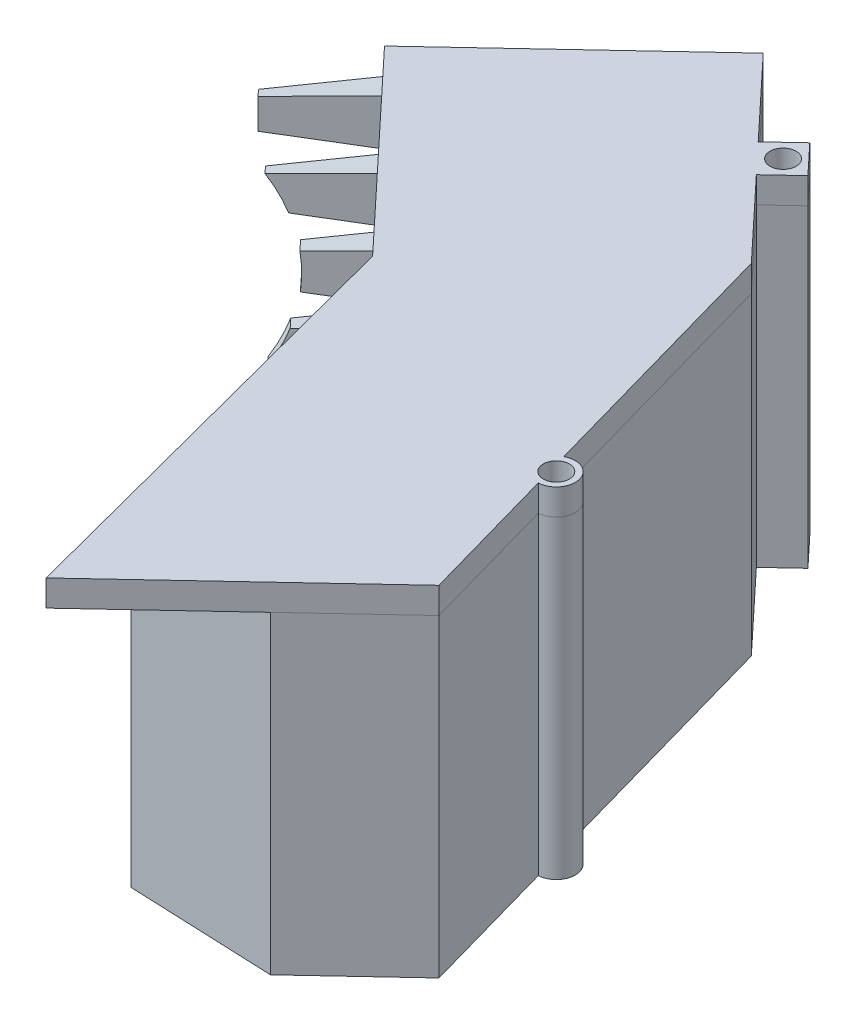
SolidWorks part; units mm, degrees
ref_plane "Front Plane" through (0, 0, 0) normal (0, 0, 1) x (1, 0, 0)
ref_plane "Top Plane" through (0, 0, 0) normal (0, 1, 0) x (1, 0, 0)
ref_plane "Right Plane" through (0, 0, 0) normal (1, 0, 0) x (0, 0, -1)
sketch "Sketch1" plane through (0, 0, 0) normal (0, 1, 0) x (1, 0, 0)
  line L0 (-4.2088, -43.4753) -> (11.4751, 13.8639) construction
  line L1 (15.2438, 108.2324) -> (-2.7837, 127.4797) construction
  line L2 (-27.496, 153.8638) -> (-74.9669, 109.4011) construction
  line L3 (11.4751, 13.8639) -> (-32.8086, 77.4293) construction
  line L4 (15.2438, 108.2324) -> (33.1183, 44.8363) construction
  line L5 (45.0177, 2.6318) -> (-4.2088, -43.4753) construction
  line L6 (-4.2088, -43.4753) -> (-32.2271, 63.7697) construction
  line L7 (45.0177, 2.6318) -> (35.5507, 36.2092)
  line L8 (15.2438, 108.2324) -> (-2.7837, 127.4797)
  line L9 (-27.496, 153.8638) -> (-74.9669, 109.4011)
  line L10 (-74.9669, 109.4011) -> (-32.2271, 63.7697)
  line L11 (-32.2271, 63.7697) -> (-4.2088, -43.4753)
  line L13 (45.0177, 2.6318) -> (-4.2088, -43.4753)
  line L15 (35.5507, 36.2092) -> (45.0177, 2.6318) construction
  line L16 (33.1183, 44.8363) -> (15.2438, 108.2324)
  line L17 (-32.8086, 77.4293) -> (-1.2, 109.0418) construction
  line L18 (20.4045, -20.4217) -> (11.4751, 13.8639) construction
  line L19 (-4.2088, -43.4753) -> (-17.3046, 6.6513) construction
  line L20 (0.3363, 130.3833) -> (0.3273, 130.3935) construction
  line L21 (-17.3046, 6.6513) -> (11.4751, 13.8639) construction
  line L22 (-6.1168, 137.7559) -> (-9.4684, 134.6166) construction
  line L23 (-3.0026, 140.4816) -> (-2.8851, 140.5844) construction
  line L24 (-17.3046, 6.6513) -> (-13.163, 7.6893) construction
  line L25 (-13.163, 7.6893) -> (-27.9465, 65.5328) construction
  line L26 (3.679, 133.5328) -> (-2.7837, 127.4797)
  line L27 (3.679, 133.5328) -> (-3.0057, 140.6698)
  line L29 (-3.0057, 140.6698) -> (-9.4684, 134.6166)
  line L30 (-51.2315, 131.6325) -> (-48.4968, 128.2564) construction
  line L31 (-48.4968, 128.2564) -> (-27.496, 147.9264) construction
  line L32 (-9.4684, 134.6166) -> (-27.496, 153.8638) construction
  line L33 (-9.4684, 134.6166) -> (-27.496, 153.8638)
  line L34 (-3.0026, 140.4816) -> (-3.0057, 140.6698) construction
  line L35 (-27.496, 147.9264) -> (-23.2222, 143.3634) construction
  line L36 (0.3273, 130.3935) -> (0.3363, 130.3833) construction
  line L37 (-23.2222, 143.3634) -> (-20.2598, 146.1381) construction
  line L38 (-23.2222, 143.3634) -> (9.6827, 108.2324) construction
  line L39 (24.1811, 76.5343) -> (20.2695, 75.4315) construction
  line L40 (20.2695, 75.4315) -> (13.2737, 100.2435) construction
  line L41 (20.2695, 75.4315) -> (27.658, 49.2262) construction
  line L42 (27.658, 49.2262) -> (31.4686, 35.7107) construction
  line L43 (31.4686, 35.7107) -> (34.5448, 24.4916) construction
  line L44 (12.1112, 105.39) -> (13.2737, 100.2435) construction
  line L45 (9.6827, 108.2324) -> (12.1112, 105.39) construction
  line L46 (-53.597, 86.5854) -> (-50.4371, 89.545) construction
  line L47 (-50.4371, 89.545) -> (-71.8071, 112.3607) construction
  line L48 (-48.4968, 128.2564) -> (-68.8447, 109.1979) construction
  line L49 (-68.8447, 109.1979) -> (-50.4371, 89.545) construction
  line L50 (-50.4371, 89.545) -> (-27.9465, 65.5328) construction
  line L51 (-68.8447, 109.1979) -> (-27.9465, 65.5328)
  line L52 (-27.9465, 65.5328) -> (-13.163, 7.6893)
  line L53 (-68.8447, 109.1979) -> (-27.496, 147.9264)
  line L54 (-27.496, 147.9264) -> (12.1112, 105.39)
  line L55 (12.1112, 105.39) -> (34.5448, 24.4916)
  arc A1 (35.5507, 36.2092) -> (33.1183, 44.8363) centre (35.3343, 40.8046) ccw
  circle A4 centre (-2.8946, 134.0748) radius 3.175
  circle A5 centre (35.3343, 40.8046) radius 3.175
  circle A6 centre (11.4751, 13.8639) radius 25.4
  circle A7 centre (-32.8086, 77.4293) radius 3.175
  circle A8 centre (-1.2, 109.0418) radius 3.175
  dimension "D1" = 6.35
  dimension "D2" = 6.35
  dimension "D3" = 59.4455
  dimension "D5" = 50.8
  dimension "D8" = 6.35
  dimension "D4" = 31.576
  dimension "D6" = 77.47
  dimension "D7" = 129.839
  dimension "D9" = 44.704
  dimension "D10" = 100.14
  dimension "D11" = 35.4294
  dimension "D12" = 4.2697
ref_plane "Plane1" through (0, 0, 0) normal (0, 1, 0) x (1, 0, 0)
sketch "Sketch4" plane through (0, 0, 0) normal (0, 1, 0) x (1, 0, 0)
  line L0 (-68.8447, 109.1979) -> (-27.9465, 65.5328)
  line L1 (-27.9465, 65.5328) -> (-13.1495, 7.6432)
  line L2 (-68.8447, 109.1979) -> (-27.496, 147.9264)
  line L3 (-27.496, 147.9264) -> (12.1112, 105.39)
  line L4 (12.1112, 105.39) -> (34.5583, 24.4455)
  circle A0 centre (-2.8946, 134.0748) radius 3.175
  circle A1 centre (35.3343, 40.8046) radius 3.175
  circle A2 centre (11.4751, 13.8639) radius 25.393
  circle A3 centre (-32.8086, 77.4293) radius 3.175
  circle A4 centre (-1.2, 109.0418) radius 3.175
extrude "Boss-Extrude2" add sketch "Sketch1" along normal blind 76.2 contours L7 A1 L16 L8 L26 L27 L29 L33 L9 L10 L11 L13 A6 L52 L51 L53 L54 L55 A5 A4 region at (18.8257, 0, 18.7361)
extrude "Boss-Extrude3" add sketch "Sketch1<5>" along normal blind 6.35 contours A6 L55 L54 L53 L51 L52 A8 A7 region at (-15.1101, 0, -86.0279)
sketch "Sketch1<5>" plane through (0, 0, 0) normal (0, 1, 0) x (1, 0, 0) same geometry as "Sketch1"
ref_plane "Plane2" through (0, 76.2, 0) normal (0, 1, 0) x (1, 0, 0)
sketch "Sketch5" plane through (0, 76.2, 0) normal (0, 1, 0) x (1, 0, 0)
  line L0 (45.0177, 2.6318) -> (35.5507, 36.2092)
  line L1 (15.2438, 108.2324) -> (-2.7837, 127.4797)
  line L2 (-27.496, 153.8638) -> (-74.9669, 109.4011)
  line L3 (-74.9669, 109.4011) -> (-32.2271, 63.7697)
  line L4 (-32.2271, 63.7697) -> (-4.2088, -43.4753)
  line L5 (45.0177, 2.6318) -> (-4.2088, -43.4753)
  line L6 (33.1183, 44.8363) -> (15.2438, 108.2324)
  line L7 (3.679, 133.5328) -> (-2.7837, 127.4797)
  line L8 (3.679, 133.5328) -> (-3.0057, 140.6698)
  line L9 (-3.0057, 140.6698) -> (-9.4684, 134.6166)
  line L10 (-9.4684, 134.6166) -> (-27.496, 153.8638)
  line L11 (45.0177, 2.6318) -> (35.5507, 36.2092) construction
  line L12 (-74.9669, 109.4011) -> (-32.2271, 63.7697) construction
  circle A1 centre (-2.8946, 134.0748) radius 3.175
  arc A3 (35.5507, 36.2092) -> (33.1183, 44.8363) centre (35.3343, 40.8046) ccw construction
  arc A4 (35.5507, 36.2092) -> (33.1183, 44.8363) centre (35.3343, 40.8046) ccw
  circle A5 centre (35.3343, 40.8046) radius 3.175
extrude "Boss-Extrude4" add sketch "Sketch5" along normal blind 6.35 separate body
ref_plane "Plane3" through (14.6497, 0, -13.7214) normal (-0.7299, 0, 0.6836) x (0.6836, 0, 0.7299)
sketch "Sketch6" plane through (14.6497, 0, -13.7214) normal (-0.7299, 0, 0.6836) x (0.6836, 0, 0.7299)
  line L0 (-99.8337, 82.55) -> (-99.8337, 0) construction
  line L4 (-99.8337, 66.675) -> (-99.8337, 15.875) construction
  line L6 (-125.2337, 66.675) -> (-74.4337, 66.675)
  line L7 (-125.2337, 66.675) -> (-125.2337, 15.875)
  line L8 (-125.2337, 15.875) -> (-74.4337, 15.875)
  line L9 (-74.4337, 66.675) -> (-74.4337, 15.875)
  line L11 (-131.0944, 82.55) -> (-68.573, 82.55) construction
  line L12 (65.9916, 0) -> (-65.9916, 0) construction
  line L13 (-131.0944, 38.1) -> (-68.573, 38.1) construction
  line L14 (-131.0944, 76.2) -> (-131.0944, 0) construction
  line L15 (-68.573, 76.2) -> (-68.573, 0) construction
  line L16 (-125.2337, 41.275) -> (-74.4337, 41.275) construction
  point P4 (-99.8337, 82.55)
  point P6 (-131.0944, 41.275)
  point P20 (-99.8337, 41.275)
  point P23 (-99.8337, 41.275)
  dimension "D1" = 50.8
  dimension "D2" = 50.8
extrude "Cut-Extrude1" cut sketch "Sketch6" against normal blind 21.59
sketch "Sketch7" plane through (14.6497, 0, -13.7214) normal (-0.7299, 0, 0.6836) x (0.6836, 0, 0.7299)
  line L0 (-125.2337, 66.675) -> (-125.2337, 15.875) construction
  line L1 (-131.0944, 76.1681) -> (-125.2337, 76.1681)
  line L2 (-131.0944, 76.1681) -> (-131.0944, 65.0458)
  line L3 (-131.0944, 65.0458) -> (-125.2337, 65.0458)
  line L4 (-125.2337, 76.1681) -> (-125.2337, 65.0458)
  line L5 (-131.0944, 48.7843) -> (-125.2337, 48.7843)
  line L6 (-125.2337, 59.9067) -> (-125.2337, 48.7843)
  line L7 (-131.0944, 59.9067) -> (-125.2337, 59.9067)
  line L8 (-131.0944, 59.9067) -> (-131.0944, 48.7843)
  line L9 (-131.0944, 32.5229) -> (-125.2337, 32.5229)
  line L10 (-125.2337, 43.6452) -> (-125.2337, 32.5229)
  line L11 (-131.0944, 43.6452) -> (-125.2337, 43.6452)
  line L12 (-131.0944, 43.6452) -> (-131.0944, 32.5229)
  line L13 (-131.0944, 16.2614) -> (-125.2337, 16.2614)
  line L14 (-125.2337, 27.3838) -> (-125.2337, 16.2614)
  line L15 (-131.0944, 27.3838) -> (-125.2337, 27.3838)
  line L16 (-131.0944, 27.3838) -> (-131.0944, 16.2614)
  line L17 (-131.0944, 0) -> (-125.2337, 0)
  line L18 (-125.2337, 11.1223) -> (-125.2337, 0)
  line L19 (-131.0944, 11.1223) -> (-125.2337, 11.1223)
  line L20 (-131.0944, 11.1223) -> (-131.0944, 0)
  line L21 (-131.0944, 0) -> (-68.573, 0) construction
  line L22 (-131.0944, 76.2) -> (-131.0944, 0) construction
  dimension "D2" = 5
extrude "Boss-Extrude5" add sketch "Sketch7" along normal blind 21.59 draft 5
ref_plane "Plane4" through (-89.6167, 0, -95.6796) normal (-0.6836, 0, -0.7299) x (-0.7299, 0, 0.6836)
sketch "Sketch10" plane through (-89.6167, 0, -95.6796) normal (-0.6836, 0, -0.7299) x (-0.7299, 0, 0.6836)
  circle A0 centre (30.057, 37.7452) radius 36.0519
extrude "Cut-Extrude2" cut sketch "Sketch10" against normal blind 21.59
ref_plane "Plane5" through (-0.4558, 0, 11.0662) normal (0.0412, 0, -0.9992) x (0, -1, 0)
sketch "Sketch11" plane through (-0.4558, 0, 11.0662) normal (0.0412, 0, -0.9992) x (0, -1, 0)
  line L1 (22.418, 79.645) -> (-79.9582, 79.645)
  line L2 (22.418, 79.645) -> (22.418, -68.9945)
  line L3 (22.418, -68.9945) -> (-79.9582, -68.9945)
  line L4 (-79.9582, 79.645) -> (-79.9582, -68.9945)
extrude "Cut-Extrude3" cut sketch "Sketch11" against normal blind 33.02 from offset 5.08 contours L2 L3 L4 L1 offset against normal yes
